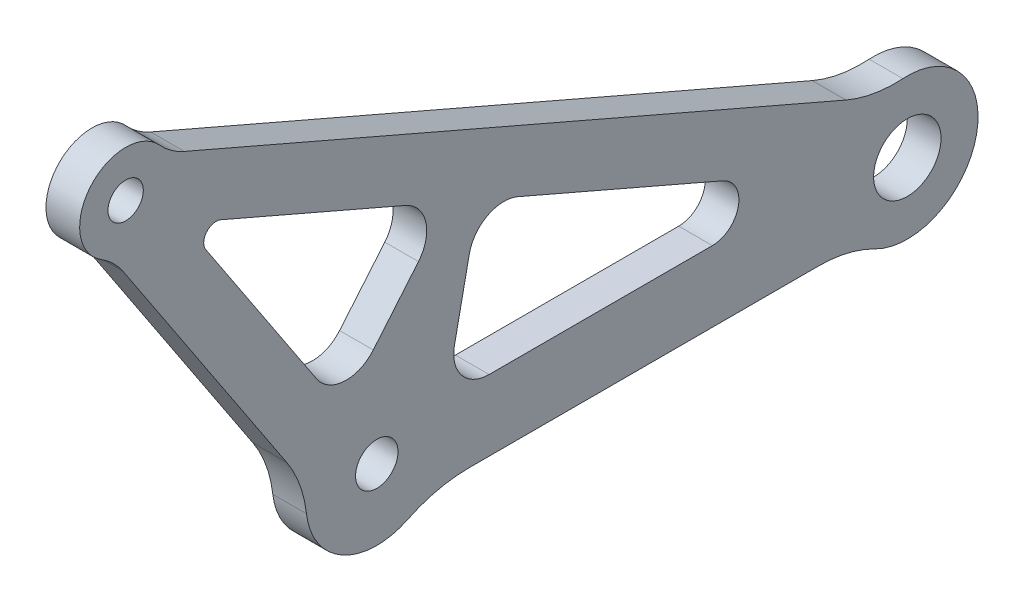
SolidWorks part; units mm, degrees
material "AISI 1020"
ref_plane "Front Plane" through (0, 0, 0) normal (0, 0, 1) x (1, 0, 0)
ref_plane "Top Plane" through (0, 0, 0) normal (0, 1, 0) x (1, 0, 0)
ref_plane "Right Plane" through (0, 0, 0) normal (1, 0, 0) x (0, 0, -1)
sketch "Sketch1" plane through (0, 0, 0) normal (1, 0, 0) x (0, 0, -1)
  line L0 (-60.7171, 0) -> (60.7171, 0)
  line L3 (0, -143.7223) -> (0, 143.7223) construction
  line L4 (-149.7529, 101.5535) -> (-94.5581, 18.1812)
  line L5 (-134.4049, 119.8783) -> (67.4524, 32.5212)
  line L6 (-75, 14) -> (75, 14) construction
  line L8 (-146, 114) -> (-75, 14) construction
  arc A20 (-134.4049, 119.8783) -> (-149.7529, 101.5535) centre (-146, 114) ccw
  arc A22 (-94.5581, 18.1812) -> (-60.7171, 0) centre (-75, 14) ccw
  arc A23 (60.7171, 0) -> (67.4524, 32.5212) centre (75, 14) ccw
  point P5 (0, 0)
  point P14 (0, 0)
  dimension "D3" = 20
  dimension "D5" = 13
  dimension "D6" = 20
  dimension "D4" = 127
  dimension "D7" = 254
  dimension "D10" = 6
  dimension "D11" = 6
  dimension "D9" = 3
  dimension "D12" = 3
  dimension "D13" = 6
  dimension "D14" = 6
  dimension "D2" = 150
  dimension "D8" = 122.6418
extrude "Boss-Extrude1" add sketch "Sketch1" along normal blind 9.525
hole_wizard "3/4 (0.75) Diameter Hole1" positions "Sketch4" profile "Sketch3" hole size "3/4" standard "ANSI Inch" end condition up to next
sketch "Sketch4" plane through (9.525, 0, 0) normal (1, 0, 0) x (0, 0, -1)
  point P5 (75, 14)
sketch "Sketch3" plane through (9.525, 14, -75) normal (0, 1, 0) x (0, 0, -1)
  line L0 (0, 0) -> (0, 9.525)
  line L1 (0, 9.525) -> (9.525, 9.525)
  line L2 (9.525, 9.525) -> (9.525, 0)
  line L5 (9.525, 0) -> (0, 0)
  line L11 (0, -6.35) -> (0, 107.95) construction
  dimension "Thru Hole Dia." = 19.05
  dimension "Thru Hole Depth" = 9.525
hole_wizard "Ø10.0 (10) Diameter Hole1" positions "Sketch9" profile "Sketch6" hole size "Ø10.0" standard "ANSI Metric" end condition up to next
sketch "Sketch9" plane through (9.525, 0, 0) normal (1, 0, 0) x (0, 0, -1)
  point P0 (-146, 114)
sketch "Sketch6" plane through (9.525, 114, 146) normal (0, 1, 0) x (0, 0, -1)
  line L0 (0, 0) -> (0, 9.525)
  line L1 (0, 9.525) -> (5, 9.525)
  line L2 (5, 9.525) -> (5, 0)
  line L5 (5, 0) -> (0, 0)
  line L11 (0, -6.35) -> (0, 107.95) construction
  dimension "Thru Hole Dia." = 10
  dimension "Thru Hole Depth" = 9.525
hole_wizard "Ø12.0 (12) Diameter Hole2" positions "Sketch15" profile "Sketch11" hole size "Ø12.0" standard "ANSI Metric" end condition up to next
sketch "Sketch15" plane through (9.525, 0, 0) normal (1, 0, 0) x (0, 0, -1)
  line L0 (75, 14) -> (157.5513, 156.983)
  line L2 (0, 0) -> (0, 108.153) construction
  line L4 (-146, 114) -> (-119.4521, 194.8786)
  line L6 (-174.545, 70.324) -> (-178.0536, 59.6351) construction
  line L7 (-174.545, 70.324) -> (-178.0536, 59.6351) construction
  arc A0 (-94.5581, 18.1812) -> (-60.7171, 0) centre (-75, 14) ccw construction
  point P0 (-75, 14)
  point P26 (0, 0)
  point P27 (-125.9054, 194.0135)
  point P28 (-125.2607, 197.072)
  point P29 (0, 0)
  dimension "D1" = 30
sketch "Sketch11" plane through (9.525, 14, 75) normal (0, 1, 0) x (0, 0, -1)
  line L0 (0, 0) -> (0, 9.525)
  line L1 (0, 9.525) -> (6, 9.525)
  line L2 (6, 9.525) -> (6, 0)
  line L5 (6, 0) -> (0, 0)
  line L11 (0, -6.35) -> (0, 107.95) construction
  dimension "Thru Hole Dia." = 12
  dimension "Thru Hole Depth" = 9.525
sketch "Sketch8" plane through (9.525, 0, 0) normal (1, 0, 0) x (0, 0, -1)
  line L2 (-54.6038, 67.909) -> (-46.3441, 64.3345) construction
  line L3 (-53.0348, 32.028) -> (-48.8351, 52.3065)
  line L7 (-75.9833, 42.3827) -> (-63.2097, 57.6339)
  line L9 (-123.3455, 90.6494) -> (-91.9879, 43.2834)
  line L10 (-119.037, 95.7935) -> (-66.9043, 73.2322)
  line L11 (19.8861, 20) -> (-43.2426, 20)
  line L12 (67.4524, 32.5212) -> (-134.4049, 119.8783) construction
  line L13 (-149.7529, 101.5535) -> (-94.5581, 18.1812) construction
  line L14 (-60.7171, 0) -> (60.7171, 0) construction
  line L15 (-84.5892, 32.1076) -> (-83.2072, 30.0201) construction
  line L16 (-55.5259, 20) -> (-58.0294, 20) construction
  line L17 (-54.6038, 67.909) -> (-46.3441, 64.3345) construction
  line L18 (-35.0712, 59.4559) -> (22.8649, 34.3831)
  line L19 (-120.4271, 92.5814) -> (-104.3957, 79.1543) construction
  line L20 (19.8861, 27.5) -> (27.9693, 25.826) construction
  line L21 (-29.8567, 10) -> (10.3311, 10) construction
  arc A0 (-53.0348, 32.028) -> (-43.2426, 20) centre (-43.2426, 30) ccw
  arc A2 (-48.8351, 52.3065) -> (-35.0712, 59.4559) centre (-39.0429, 50.2785) cw
  arc A4 (-63.2097, 57.6339) -> (-66.9043, 73.2322) centre (-70.876, 64.0548) ccw
  arc A14 (-119.037, 95.7935) -> (-123.3455, 90.6494) centre (-120.4271, 92.5814) ccw
  arc A20 (-75.9833, 42.3827) -> (-91.9879, 43.2834) centre (-83.6496, 48.8036) cw
  arc A25 (-134.4049, 119.8783) -> (-149.7529, 101.5535) centre (-146, 114) ccw construction
  circle A27 centre (-146, 114) radius 5 construction
  arc A36 (-94.5581, 18.1812) -> (-60.7171, 0) centre (-75, 14) ccw construction
  circle A39 centre (-75, 14) radius 6 construction
  arc A40 (19.8861, 20) -> (22.8649, 34.3831) centre (19.8861, 27.5) ccw
  circle A54 centre (-75, 14) radius 18
  arc A55 (-58.0294, 20) -> (-83.2072, 30.0201) centre (-75, 14) ccw construction
  point P7 (-33.5049, 66.1162)
  point P19 (-33.4763, 76.1997)
  dimension "D8" = 8
  dimension "D9" = 14
  dimension "D11" = 9
  dimension "D7" = 4
  dimension "D1" = 7
  dimension "D10" = 24.8576
  dimension "D2" = 15
  dimension "D12" = 10
  dimension "D13" = 14.6862
  dimension "D3" = 12
  dimension "D5" = 16
  dimension "D6" = 20
  dimension "D4" = 16
extrude "Cut-Extrude1" cut sketch "Sketch8" against normal up to next
fillet "Fillet1" radius 35 1 edges at (4.7625, 18.1812, 94.5581)
fillet "Fillet3" radius 35 2 edges at (4.7625, 32.5212, -67.4524) (4.7625, 0, -60.7171)
fillet "Fillet4" radius 20 2 edges at (4.7625, 101.5535, 149.7529) (4.7625, 119.8783, 134.4049)
fillet "Fillet6" radius 40 1 edges at (4.7625, 0, 60.7171)
equation "\"D11@Sketch1\"=\"D10@Sketch1\""
equation "\"D12@Sketch1\"=\"D9@Sketch1\""
equation "\"D14@Sketch1\"=\"D13@Sketch1\""
